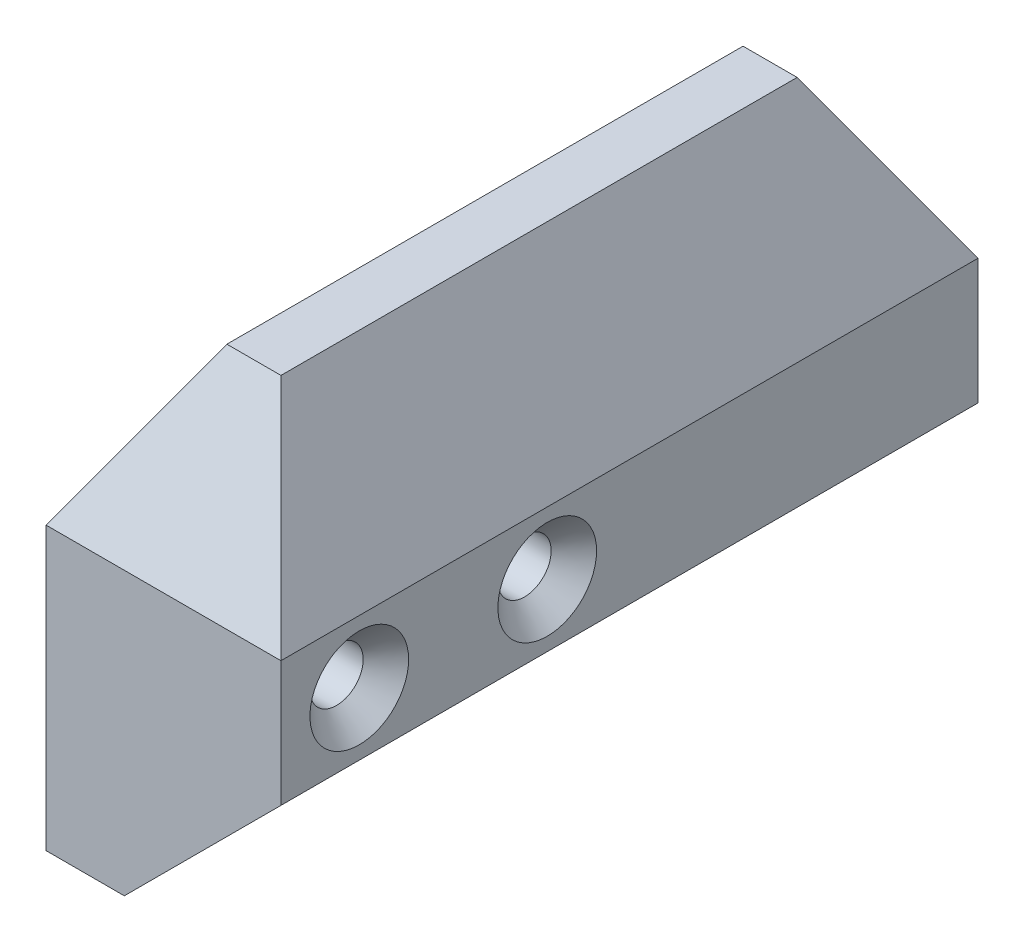
SolidWorks part; units mm, degrees
ref_plane "Plan de face" through (0, 0, 0) normal (0, 0, 1) x (1, 0, 0)
ref_plane "Plan de dessus" through (0, 0, 0) normal (0, 1, 0) x (1, 0, 0)
ref_plane "Plan de droite" through (0, 0, 0) normal (1, 0, 0) x (0, 0, -1)
sketch "Esquisse1" plane through (0, 0, 0) normal (0, 0, 1) x (1, 0, 0)
  line L0 (0, 8) -> (5.7735, 18)
  line L1 (0, 0) -> (15, 0)
  line L2 (0, 0) -> (0, 8)
  line L3 (5.7735, 18) -> (9.2265, 18)
  line L4 (15, 0) -> (15, 8)
  line L5 (9.2265, 18) -> (15, 8)
  point P6 (40, 6.1203)
  dimension "D1" = 15
  dimension "D2" = 8
  dimension "D3" = 150
  dimension "D4" = 10
extrude "Boss.-Extru.1" add sketch "Esquisse1" along normal blind 44.5
ref_plane "Plan1" through (0, 21.2691, 36.8391) normal (0, 0.5, 0.866) x (-1, 0, 0)
ref_axis "Axe1" through (21.665, 18, 38.7265) along (-1, 0, 0)
sketch "Esquisse2" plane through (0, 21.2691, 36.8391) normal (0, 0.5, 0.866) x (-1, 0, 0)
  line L1 (0, 15.3218) -> (-15, 15.3218)
  line L2 (0, 15.3218) -> (0, 3.7748)
  line L3 (0, 3.7748) -> (-15, 3.7748)
  line L4 (-15, 15.3218) -> (-15, 3.7748)
  line L5 (-21.665, 3.7748) -> (-2.6455, 3.7748) construction
  point P5 (0, 0)
  point P7 (0, 4.1411)
  point P8 (-15, 4.1411)
extrude "Enlèv. mat.-Extru.1" cut sketch "Esquisse2" along normal through all
ref_plane "Plan3" through (0, 2, -3.4641) normal (0, 0.5, -0.866) x (-1, 0, 0)
ref_axis "Axe2" through (9.2265, 18, 5.7735) along (-1, 0, 0)
sketch "Esquisse4" plane through (0, 2, -3.4641) normal (0, 0.5, -0.866) x (-1, 0, 0)
  line L0 (-9.2265, 18.4752) -> (-5.7735, 18.4752) construction
  line L1 (-15, 6.9282) -> (0, 6.9282)
  line L2 (-15, 6.9282) -> (-15, 18.4752)
  line L3 (-15, 18.4752) -> (0, 18.4752)
  line L4 (0, 6.9282) -> (0, 18.4752)
  point P5 (0, 4.3301)
extrude "Enlèv. mat.-Extru.3" cut sketch "Esquisse4" along normal through all
sketch "Esquisse5" plane through (0, 0, 0) normal (0, 0, 1) x (1, 0, 0)
  line L0 (0, -10) -> (5, -10)
  line L1 (0, 0) -> (15, 0)
  line L2 (0, 0) -> (0, -10)
  line L3 (5, -10) -> (15, 0)
  line L4 (15, 0) -> (15, 8) construction
  point P3 (6.0618, -8.9382)
  point P5 (15, 0)
  point P9 (15.1396, 0)
  dimension "D1" = 135
  dimension "D2" = 5
extrude "Boss.-Extru.4" add sketch "Esquisse5" along normal up to surface (44.5 mm away) up to face at (7.5, 4, 44.5)
hole_wizard "Fraisage pour vis à tête fraisée M31" positions "Esquisse7" profile "Esquisse6" countersink size "M3" standard "Ansi Metric" end condition through all
sketch "Esquisse7" plane through (15, 0, 0) normal (1, 0, 0) x (0, 0, -1)
  line L0 (-44.5, 0) -> (-44.5, 8) construction
  point P0 (-39.5, 4)
  point P7 (-37.7413, 0)
  point P12 (0, 0)
  point P13 (-44.5, 4)
  dimension "D1" = 5
sketch "Esquisse6" plane through (15, 4, 39.5) normal (0, 1, 0) x (0, 0, -1)
  line L0 (0, 0) -> (0, 15)
  line L1 (0, 15) -> (1.7, 15)
  line L2 (1.7, 15) -> (1.7, 1.45)
  line L3 (1.7, 1.45) -> (3.15, 0)
  line L5 (3.15, 0) -> (0, 0)
  line L6 (-1.7, 1.45) -> (-3.15, 0) construction
  line L11 (0, -6.35) -> (0, 107.95) construction
  dimension "Diamètre du perçage jusqu'au prochain" = 3.4
  dimension "Profondeur du perçage jusqu'au prochain" = 15
  dimension "Diamètre du fraisage entrant" = 6.3
  dimension "Angle du fraisage entrant" = 90
pattern_linear "Répétition linéaire1" count 2 spacing 12 along (0, 0, -1) of "Fraisage pour vis à tête fraisée M31"
